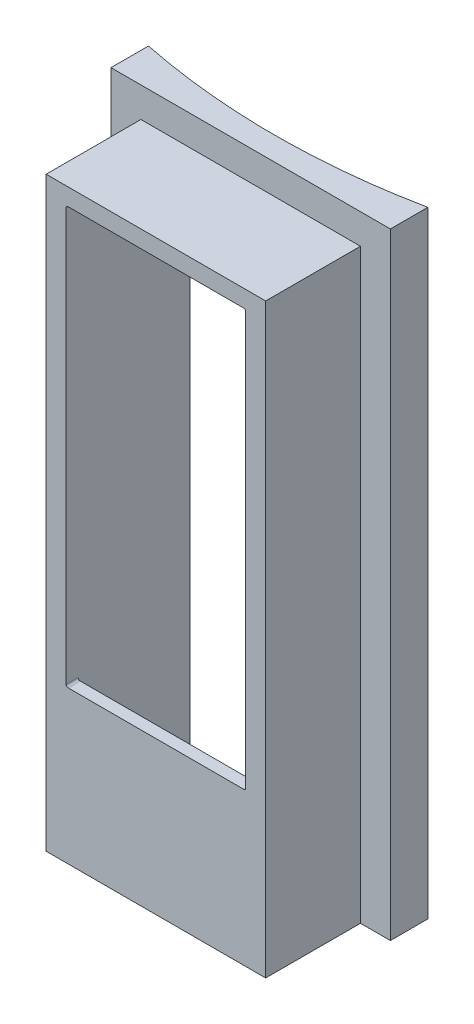
SolidWorks part; units mm, degrees
ref_plane "Front Plane" through (0, 0, 0) normal (0, 0, 1) x (1, 0, 0)
ref_plane "Top Plane" through (0, 0, 0) normal (0, 1, 0) x (1, 0, 0)
ref_plane "Right Plane" through (0, 0, 0) normal (1, 0, 0) x (0, 0, -1)
sketch "Sketch1" plane through (0, 0, 0) normal (0, 0, 1) x (1, 0, 0)
  line L1 (-44.45, 95.885) -> (44.45, 95.885)
  line L2 (-44.45, 95.885) -> (-44.45, -100.203)
  line L3 (-44.45, -100.203) -> (44.45, -100.203)
  line L4 (44.45, 95.885) -> (44.45, -100.203)
  point P5 (0, 95.885)
  dimension "D1" = 88.9
  dimension "D2" = 196.088
extrude "Extrude1" add sketch "Sketch1" along normal blind 230.2002
sketch "Sketch5" plane through (0, 0, 230.2002) normal (0, 0, 1) x (1, 0, 0)
  line L0 (44.45, 95.885) -> (-44.45, 95.885) construction
  line L1 (-34.925, 86.36) -> (34.925, 86.36)
  line L2 (-34.925, 86.36) -> (-34.925, -100.203)
  line L3 (-34.925, -100.203) -> (34.925, -100.203)
  line L4 (34.925, 86.36) -> (34.925, -100.203)
  line L5 (0, 95.885) -> (0, -100.203) construction
  line L8 (-44.45, -100.203) -> (44.45, -100.203) construction
  point P4 (0, -100.203)
  point P5 (0, 95.885)
  point P11 (0, 86.36)
  dimension "D1" = 69.85
  dimension "D2" = 9.525
extrude "Extrude4" add sketch "Sketch5" along normal blind 30.1523
sketch "Sketch2" plane through (0, 95.885, 0) normal (0, 1, 0) x (-1, 0, 0)
  line L0 (-44.45, 0) -> (44.45, 0) construction
  circle A1 centre (0, 0) radius 222.758
sketch "Sketch4" plane through (0, 0, 230.2002) normal (0, 0, 1) x (1, 0, 0)
  line L0 (34.925, 86.36) -> (-34.925, 86.36) construction
  line L1 (-28.575, 80.899) -> (28.575, 80.899)
  line L2 (-28.575, 80.899) -> (-28.575, -51.689)
  line L3 (-28.575, -51.689) -> (28.575, -51.689)
  line L4 (28.575, 80.899) -> (28.575, -51.689)
  point P4 (0, -51.689)
  point P5 (0, 80.899)
  point P6 (0, 0)
  dimension "D1" = 57.15
  dimension "D2" = 5.461
  dimension "D3" = 132.588
extrude "Extrude2" cut sketch "Sketch4" against normal blind 273.8502 and the other way blind 93.98
sketch "Sketch6" plane through (0, 0, 0) normal (0, 0, -1) x (-1, 0, 0)
  line L0 (-28.575, -51.689) -> (28.575, -51.689) construction
  line L1 (-28.575, -51.689) -> (28.575, -51.689)
  line L2 (-28.575, -51.689) -> (-28.575, -97.663)
  line L3 (-28.575, -97.663) -> (28.575, -97.663)
  line L4 (28.575, -51.689) -> (28.575, -97.663)
  line L6 (-28.575, 80.899) -> (28.575, 80.899)
  line L7 (-28.575, 80.899) -> (-28.575, 83.82)
  line L8 (-28.575, 83.82) -> (28.575, 83.82)
  line L9 (28.575, 80.899) -> (28.575, 83.82)
  line L10 (44.45, -100.203) -> (-44.45, -100.203) construction
  line L11 (-44.45, 95.885) -> (44.45, 95.885) construction
  point P4 (0, -100.203)
  point P6 (0, -51.689)
  point P13 (0, -100.203)
  point P15 (0, 95.885)
  point P19 (0, 80.899)
  point P22 (0, -97.663)
  dimension "D1" = 57.15
  dimension "D2" = 2.921
extrude "Extrude5" cut sketch "Sketch6" against normal blind 256.54
fillet "Fillet1" radius 2.54 4 edges at (-28.575, -97.663, 128.27) (28.575, -97.663, 128.27) (-28.575, 83.82, 128.27) (28.575, 83.82, 128.27)
extrude "Extrude3" cut sketch "Sketch2" against normal blind 202.86
sketch "Sketch7" plane through (0, 0, 260.3525) normal (0, 0, 1) x (1, 0, 0)
fillet "Fillet2" radius 0.635 4 edges at (28.575, 80.899, 258.4463) (-28.575, 80.899, 258.4463) (-28.575, -51.689, 258.4463) (28.575, -51.689, 258.4463)
sketch "Sketch8" plane through (0, 0, 260.3525) normal (0, 0, 1) x (1, 0, 0)
